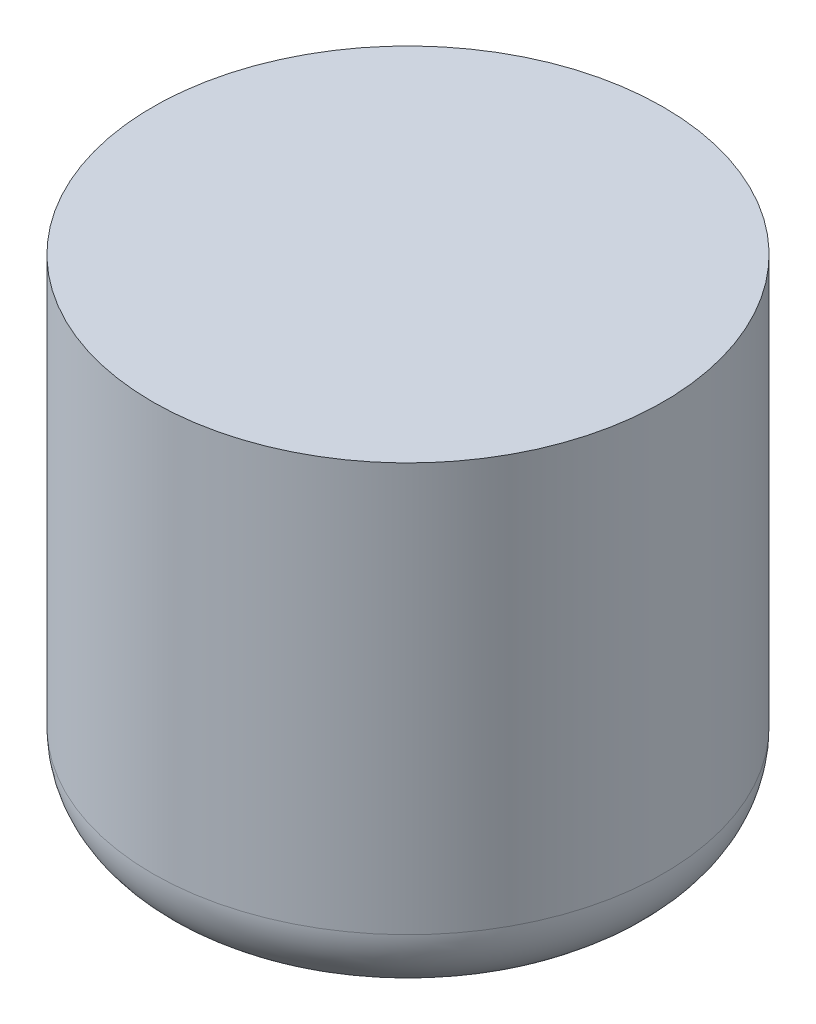
SolidWorks part; units mm, degrees
ref_plane "Front Plane" through (0, 0, 0) normal (0, 0, 1) x (1, 0, 0)
ref_plane "Top Plane" through (0, 0, 0) normal (0, 1, 0) x (1, 0, 0)
ref_plane "Right Plane" through (0, 0, 0) normal (1, 0, 0) x (0, 0, -1)
sketch "Sketch1" plane through (0, 0, 0) normal (0, 0, 1) x (1, 0, 0)
  line L0 (0, 170) -> (0, 770)
  line L1 (0, 770) -> (375, 770)
  line L2 (375, 770) -> (375, 170)
  line L3 (0, 170) -> (0, 0)
  line L4 (200, 31.3778) -> (200, 770) construction
  line L5 (200, 770) -> (200, 970) construction
  arc A2 (375, 170) -> (305, 70) centre (268.5714, 170) cw
  arc A3 (0, 0) -> (305, 70) centre (-22.9979, 799.6694) ccw
  dimension "D7" = 800
  dimension "D1" = 600
  dimension "D2" = 375
  dimension "D3" = 600
  dimension "D4" = 170
  dimension "D5" = 100
  dimension "D6" = 70
  dimension "D8" = 200
  dimension "D9" = 738.6222
  dimension "D10" = 200
revolve "Revolve1" add sketch "Sketch1" angle 360 about L0
